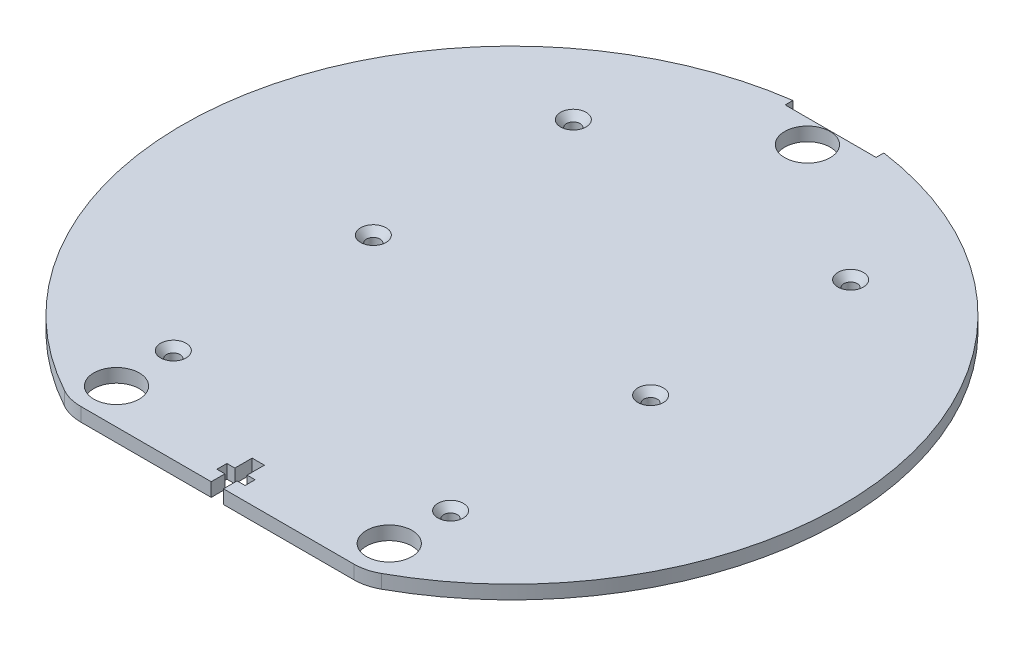
SolidWorks part; units mm, degrees
material "ABS"
ref_plane "Front Plane" through (0, 0, 0) normal (0, 0, 1) x (1, 0, 0)
ref_plane "Top Plane" through (0, 0, 0) normal (0, 1, 0) x (1, 0, 0)
ref_plane "Right Plane" through (0, 0, 0) normal (1, 0, 0) x (0, 0, -1)
sketch "Sketch1" plane through (0, 0, 0) normal (0, 1, 0) x (1, 0, 0)
  line L0 (0, -85) -> (0, 0) construction
  line L1 (30.03, -64.8129) -> (-30.03, -64.8129)
  arc A0 (34.8348, -63.5829) -> (-34.8348, -63.5829) centre (0, 0) ccw
  circle A1 centre (0, -85) radius 38.25 construction
  arc A2 (30.03, -64.8129) -> (34.8348, -63.5829) centre (30.03, -54.8129) ccw
  arc A3 (-30.03, -64.8129) -> (-34.8348, -63.5829) centre (-30.03, -54.8129) cw
  point P12 (-32.4891, -64.8129)
  dimension "D1" = 145
  dimension "D3" = 76.5
  dimension "D4" = 10
  dimension "D2" = 85
extrude "Boss-Extrude1" add sketch "Sketch1" along normal blind 3
sketch "Sketch2" plane through (0, 3, 0) normal (0, 1, 0) x (1, 0, 0)
  line L1 (-30.5, -44) -> (30.5, -44) construction
  line L2 (-30.5, -44) -> (-30.5, 44) construction
  line L3 (-30.5, 44) -> (30.5, 44) construction
  line L4 (30.5, -44) -> (30.5, 44) construction
  line L5 (-30.5, -44) -> (30.5, 44) construction
  line L6 (-30.5, 44) -> (30.5, -44) construction
  circle A0 centre (-30.5, 44) radius 1.5
  circle A1 centre (30.5, 44) radius 1.5
  circle A2 centre (30.5, 0) radius 1.5
  circle A3 centre (30.5, -44) radius 1.5
  circle A4 centre (-30.5, -44) radius 1.5
  circle A5 centre (-30.5, 0) radius 1.5
  point P0 (0, 0)
  dimension "D3" = 3
  dimension "D1" = 61
  dimension "D2" = 88
extrude "Cut-Extrude1" cut sketch "Sketch2" against normal through all
chamfer "Chamfer1" distance 1.5 angle 41 6 edges at (30.5, 3, -42.5) (30.5, 3, 1.5) (30.5, 3, 45.5) (-30.5, 3, 45.5) (-30.5, 3, 1.5) (-30.5, 3, -42.5) first distance on face at (30.5, 0, -42.5) first distance on face at (30.5, 0, 1.5) first distance on face at (30.5, 0, 45.5) first distance on face at (-30.5, 0, 45.5) first distance on face at (-30.5, 0, 1.5) first distance on face at (-30.5, 0, -42.5)
sketch "Sketch3" plane through (0, 3, 0) normal (0, 1, 0) x (1, 0, 0)
  line L0 (-30.03, -64.8129) -> (30.03, -64.8129) construction
  line L1 (1.35, -61.8129) -> (3.1, -61.8129)
  line L2 (-3.1, -59.6129) -> (-1.35, -59.6129)
  line L3 (-3.1, -59.6129) -> (-3.1, -61.8129)
  line L4 (-3.1, -61.8129) -> (-1.35, -61.8129)
  line L5 (3.1, -59.6129) -> (3.1, -61.8129)
  line L6 (-1.35, -64.8129) -> (1.35, -64.8129)
  line L7 (-1.35, -64.8129) -> (-1.35, -61.8129)
  line L8 (1.35, -59.6129) -> (3.1, -59.6129)
  line L9 (1.35, -64.8129) -> (1.35, -61.8129)
  line L11 (-1.35, -59.6129) -> (-1.35, -55.8129)
  line L12 (-1.35, -55.8129) -> (1.35, -55.8129)
  line L13 (1.35, -59.6129) -> (1.35, -55.8129)
  point P10 (0, -64.8129)
  point P14 (0, -64.8129)
  dimension "D1" = 2.7
  dimension "D2" = 6.2
  dimension "D3" = 2.2
  dimension "D4" = 3
  dimension "D5" = 9
extrude "Cut-Extrude2" cut sketch "Sketch3" against normal through all
sketch "Sketch4" plane through (0, 3, 0) normal (0, 1, 0) x (1, 0, 0)
  line L1 (-10, 71.807) -> (10, 71.807)
  line L2 (-10, 71.807) -> (-10, 70.107)
  line L3 (-10, 70.107) -> (10, 70.107)
  line L4 (10, 71.807) -> (10, 70.107)
  arc A0 (34.8348, -63.5829) -> (-34.8348, -63.5829) centre (0, 0) ccw construction
  dimension "D1" = 1.7
  dimension "D2" = 20
extrude "Cut-Extrude3" cut sketch "Sketch4" against normal through all
sketch "Sketch5" plane through (0, 3, 0) normal (0, 1, 0) x (1, 0, 0)
  line L0 (0, 0) -> (0, 65) construction
  circle A0 centre (0, 65) radius 5
  circle A1 centre (30, -57) radius 5
  circle A2 centre (-30, -57) radius 5
  dimension "D1" = 10
  dimension "D2" = 65
  dimension "D3" = 57
  dimension "D4" = 30
extrude "Cut-Extrude4" cut sketch "Sketch5" against normal through all
equation "\"smallPulleyTeeth\"= 30"
equation "\"largePulleyTeeth\"= 30"
equation "\"eighthThick\"= 3.0mm"
equation "\"sixteenthThick\"= 1.7mm"
equation "\"quarterThick\"=6.0mm"
equation "\"OD\"= 145mm"
equation "\"puckAngle\"= 60.5deg"
equation "\"puckDiam\"= 76.5mm"
equation "\"puckDist\"= 85mm"
equation "\"scoopFillet\"= 5mm"
equation "\"axlePress\"= 5.9mm"
equation "\"press\"= 0.2mm"
equation "\"wheelClear\"= 0.3mm"
equation "\"10-32clear\"= 4.8mm"
equation "\"10-32tap\"= 4.45mm"
equation "\"6-32clear\"= 3.3mm"
equation "\"8-32clear\"= 4.0mm"
equation "\"4-40clear\"= 3.0mm"
equation "\"wheelHeight\"= 22mm"
equation "\"wheelWell\"= 65mm"
equation "\"ledSmall\"= 3.1mm"
equation "\"ledLarge\"= 4.2mm"
equation "\"ledLength\"= 4.2mm"
equation "\"D1@Sketch1\"=\"OD\""
equation "\"D1@Boss-Extrude1\"=\"eighthThick\""
equation "\"D3@Sketch2\"=\"4-40clear\""
equation "\"D3@Sketch1\"=\"puckDiam\""
equation "\"D2@Sketch1\"=\"puckDist\""
equation "\"4-40close\"= 2.7mm"
equation "\"4-40nutThick\"= 2.2mm"
equation "\"4-40nutWidth\"= 6.2mm"
equation "\"D1@Sketch4\"=\"sixteenthThick\""
equation "\"D1@Sketch3\"=\"4-40close\""
equation "\"4-40insertHeight\"= 3.5mm"
equation "\"4-40insert\"= 4mm"
equation "\"D2@Sketch3\"=\"4-40nutWidth\""
equation "\"D3@Sketch3\"=\"4-40nutThick\""
